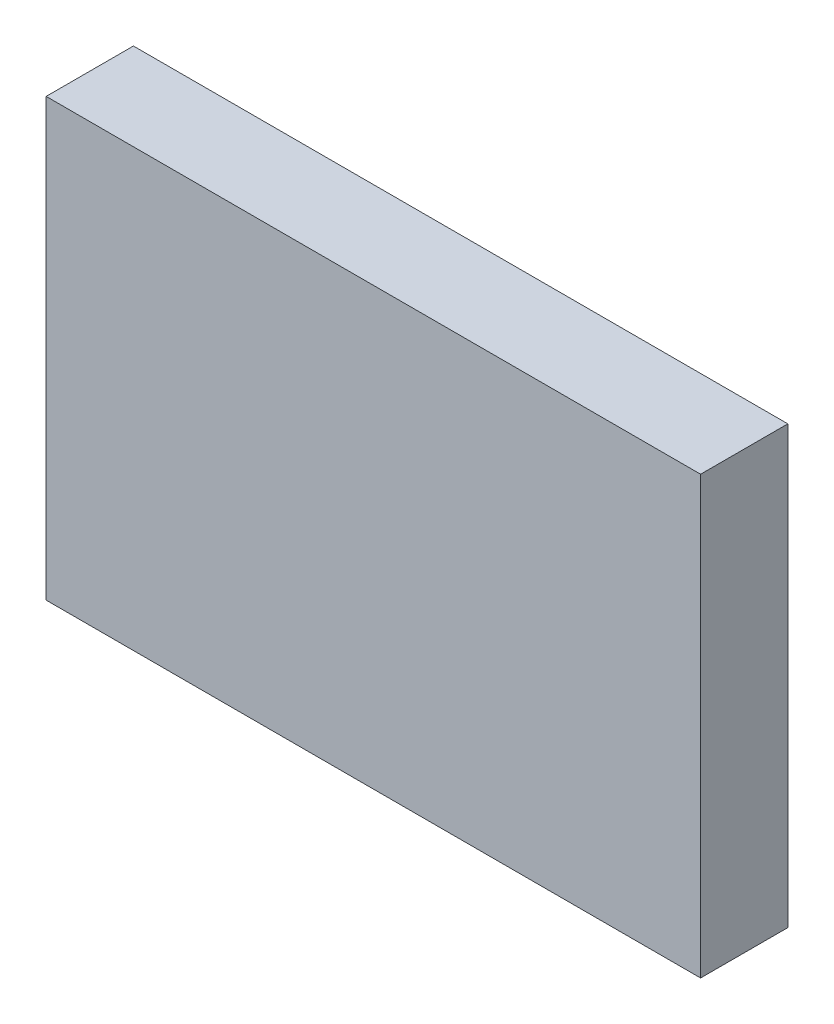
SolidWorks part; units mm, degrees
ref_plane "Front Plane" through (0, 0, 0) normal (0, 0, 1) x (1, 0, 0)
ref_plane "Top Plane" through (0, 0, 0) normal (0, 1, 0) x (1, 0, 0)
ref_plane "Right Plane" through (0, 0, 0) normal (1, 0, 0) x (0, 0, -1)
sketch "Sketch2" plane through (0, 0, 0) normal (0, 0, 1) x (1, 0, 0)
  line L0 (0, 0) -> (0, 20)
  line L1 (0, 20) -> (30, 20)
  line L2 (30, 20) -> (30, 0)
  line L3 (30, 0) -> (0, 0)
  dimension "D1" = 30
  dimension "D2" = 20
extrude "Boss-Extrude1" add sketch "Sketch2" along normal blind 4 contours L3 L0 L1 L2
